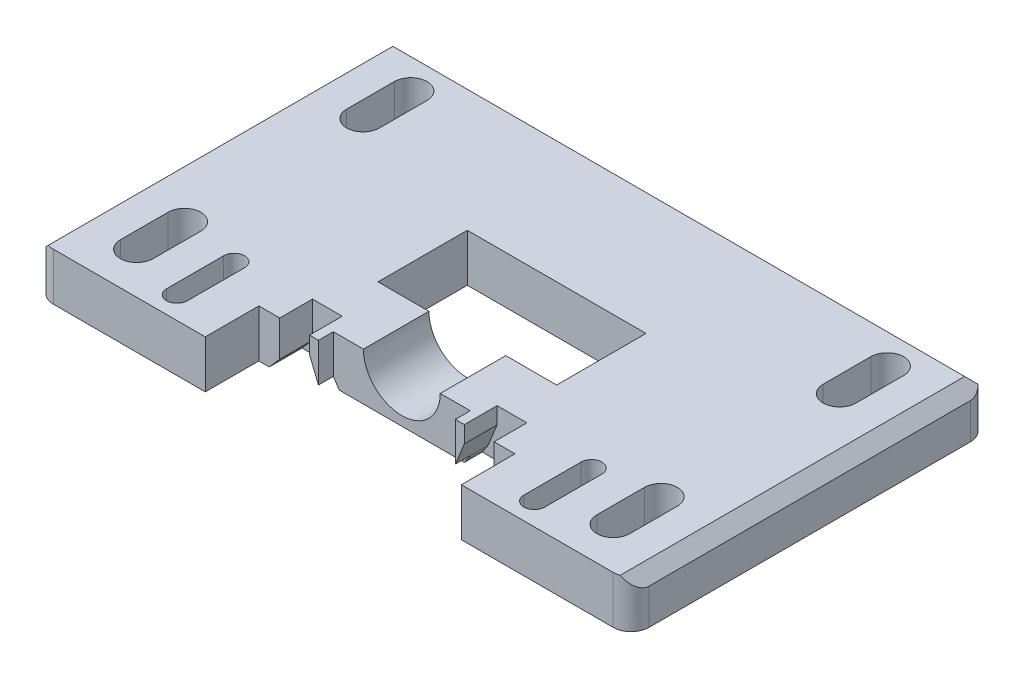
SolidWorks part; units mm, degrees
ref_plane "Front Plane" through (0, 0, 0) normal (0, 0, 1) x (1, 0, 0)
ref_plane "Top Plane" through (0, 0, 0) normal (0, 1, 0) x (1, 0, 0)
ref_plane "Right Plane" through (0, 0, 0) normal (1, 0, 0) x (0, 0, -1)
sketch "Sketch1" plane through (0, 0, 0) normal (0, 1, 0) x (1, 0, 0)
  line L0 (40, 23) -> (40, 15) construction
  line L1 (-50, 30) -> (50, 30)
  line L2 (-50, 30) -> (-50, -30)
  line L3 (-50, -30) -> (50, -30)
  line L4 (50, 30) -> (50, -30)
  line L5 (-15, -7.5) -> (15, -7.5)
  line L6 (-15, -7.5) -> (-15, 7.5)
  line L7 (-15, 7.5) -> (15, 7.5)
  line L8 (15, -7.5) -> (15, 7.5)
  line L9 (-15, -7.5) -> (15, 7.5) construction
  line L10 (-15, 7.5) -> (15, -7.5) construction
  line L11 (42.75, 23) -> (42.75, 15)
  line L12 (37.25, 23) -> (37.25, 15)
  line L13 (40, -23) -> (40, -15) construction
  line L14 (37.25, -23) -> (37.25, -15)
  line L15 (42.75, -23) -> (42.75, -15)
  line L16 (-40, -15) -> (-40, -23) construction
  line L17 (-37.25, -15) -> (-37.25, -23)
  line L18 (-42.75, -15) -> (-42.75, -23)
  line L19 (-40, 23) -> (-40, 15) construction
  line L20 (-37.25, 23) -> (-37.25, 15)
  line L21 (-42.75, 23) -> (-42.75, 15)
  line L22 (-30, -26.25) -> (-30, -16.652) construction
  line L23 (-21.5, -30) -> (21.5, -30)
  line L24 (-21.5, -30) -> (-21.5, -21)
  line L25 (-21.5, -21) -> (21.5, -21)
  line L26 (21.5, -30) -> (21.5, -21)
  line L27 (11.5, -21) -> (-11.5, -21)
  line L28 (11.5, -21) -> (11.5, -18.5)
  line L29 (11.5, -18.5) -> (-11.5, -18.5)
  line L30 (-11.5, -21) -> (-11.5, -18.5)
  line L31 (-31.75, -26.25) -> (-31.75, -16.652)
  line L32 (-28.25, -26.25) -> (-28.25, -16.652)
  line L33 (30, -16.65) -> (30, -26.25) construction
  line L34 (31.75, -16.65) -> (31.75, -26.25)
  line L35 (28.25, -16.65) -> (28.25, -26.25)
  line L37 (13, -21) -> (18, -21)
  line L38 (13, -21) -> (13, -15.5)
  line L39 (13, -15.5) -> (18, -15.5)
  line L40 (18, -21) -> (18, -15.5)
  line L41 (-13, -21) -> (-18, -21)
  line L42 (-13, -21) -> (-13, -15.5)
  line L43 (-13, -15.5) -> (-18, -15.5)
  line L44 (-18, -21) -> (-18, -15.5)
  circle A0 centre (-40, 19) radius 2.75
  circle A1 centre (-40, 19) radius 11.95 construction
  circle A2 centre (40, 19) radius 2.75
  circle A3 centre (-40, -19) radius 2.75
  circle A4 centre (40, -19) radius 2.75
  arc A5 (42.75, 23) -> (37.25, 23) centre (40, 23) ccw
  arc A6 (37.25, 15) -> (42.75, 15) centre (40, 15) ccw
  arc A7 (37.25, -23) -> (42.75, -23) centre (40, -23) ccw
  arc A8 (42.75, -15) -> (37.25, -15) centre (40, -15) ccw
  arc A9 (-37.25, -15) -> (-42.75, -15) centre (-40, -15) ccw
  arc A10 (-42.75, -23) -> (-37.25, -23) centre (-40, -23) ccw
  arc A11 (-37.25, 23) -> (-42.75, 23) centre (-40, 23) ccw
  arc A12 (-42.75, 15) -> (-37.25, 15) centre (-40, 15) ccw
  arc A13 (-31.75, -26.25) -> (-28.25, -26.25) centre (-30, -26.25) ccw
  arc A14 (-28.25, -16.652) -> (-31.75, -16.652) centre (-30, -16.652) ccw
  arc A15 (31.75, -16.65) -> (28.25, -16.65) centre (30, -16.65) ccw
  arc A16 (28.25, -26.25) -> (31.75, -26.25) centre (30, -26.25) ccw
  point P14 (0, 0)
  point P21 (40, 19)
  point P28 (40, -19)
  point P35 (-40, -19)
  point P42 (-40, 19)
  point P51 (0, -21)
  point P56 (0, -18.5)
  point P59 (-30, -21.451)
  point P66 (30, -21.45)
  dimension "D5" = 5.5
  dimension "D8" = 23.9
  dimension "D9" = 5.5
  dimension "D10" = 10
  dimension "D12" = 5.5
  dimension "D13" = 11
  dimension "D14" = 10
  dimension "D15" = 11
  dimension "D16" = 5.5
  dimension "D33" = 10
  dimension "D1" = 60
  dimension "D2" = 100
  dimension "D3" = 50
  dimension "D4" = 30
  dimension "D6" = 10
  dimension "D7" = 11
  dimension "D11" = 11
  dimension "10" = 10
  dimension "D17" = 15
  dimension "D18" = 30
  dimension "D19" = 5.5
  dimension "D20" = 8
  dimension "D21" = 5.5
  dimension "D22" = 8
  dimension "D23" = 5.5
  dimension "D24" = 8
  dimension "D25" = 5.5
  dimension "D26" = 8
  dimension "D27" = 43
  dimension "D28" = 9
  dimension "D29" = 2.5
  dimension "D30" = 23
  dimension "D31" = 3.5
  dimension "D32" = 9.598
  dimension "D34" = 3.75
  dimension "D35" = 3.5
  dimension "D36" = 9.6
  dimension "D37" = 10
  dimension "D38" = 3.75
  dimension "D39" = 13
  dimension "D40" = 5
  dimension "D41" = 5.5
  dimension "D42" = 5
  dimension "D43" = 13
  dimension "D44" = 5.5
sketch "Sketch2" plane through (0, 0, 0) normal (0, 1, 0) x (1, 0, 0)
  line L0 (-100, -10) -> (100, 10) construction
  line L1 (-100, 10) -> (100, 10) construction
  line L2 (-100, 10) -> (-100, -10) construction
  line L3 (-100, -10) -> (100, -10) construction
  line L4 (100, 10) -> (100, -10) construction
  dimension "D1" = 200
  dimension "D2" = 20
extrude "Boss-Extrude1" add sketch "Sketch1" along normal blind 8 contours L4 L1 L2 L3 A12 L21 A11 L20 A10 L18 A9 L17 A8 L15 A7 L14 A6 L12 A5 L11 L8 L5 L6 L7 region at (0, 0, -28.8338)
sketch "Sketch4" plane through (0, 0, 18.5) normal (0, 0, 1) x (1, 0, 0)
  line L0 (11.5, 8) -> (-11.5, 8) construction
  circle A0 centre (0, 8) radius 6.45
  dimension "D1" = 12.9
extrude "Cut-Extrude1" cut sketch "Sketch4" against normal up to surface (11 mm away) up to face at (0, 4, 7.5)
sketch "Sketch5" plane through (0, 0, 21) normal (0, 0, 1) x (1, 0, 0)
  line L0 (13, 5.2) -> (11.5, 1.5)
  line L2 (11.5, 8) -> (11.5, 0) construction
  line L3 (18, 2) -> (19.75, 0)
  line L4 (18, 8) -> (18, 0) construction
  line L5 (18, 0) -> (21.5, 0) construction
  line L6 (21.5, 0) -> (21.5, 8) construction
  line L7 (21.5, 8) -> (18, 8) construction
  line L8 (11.5, 0) -> (13, 0) construction
  line L9 (13, 0) -> (13, 8) construction
  line L10 (13, 8) -> (11.5, 8) construction
  line L11 (18, 0) -> (21.5, 0)
  line L12 (21.5, 0) -> (21.5, 8)
  line L13 (21.5, 8) -> (18, 8)
  line L14 (18, 8) -> (18, 0)
  line L15 (11.5, 0) -> (13, 0)
  line L16 (13, 0) -> (13, 8)
  line L17 (13, 8) -> (11.5, 8)
  line L18 (11.5, 8) -> (11.5, 0)
  line L19 (13, 8) -> (13, 0) construction
  line L21 (-21.5, 0) -> (-18, 0) construction
  line L22 (-18, 0) -> (-18, 8) construction
  line L23 (-18, 8) -> (-21.5, 8) construction
  line L24 (-21.5, 8) -> (-21.5, 0) construction
  line L25 (-13, 0) -> (-11.5, 0) construction
  line L26 (-11.5, 0) -> (-11.5, 8) construction
  line L27 (-11.5, 8) -> (-13, 8) construction
  line L28 (-13, 8) -> (-13, 0) construction
  line L29 (-21.5, 0) -> (-18, 0)
  line L30 (-18, 0) -> (-18, 8)
  line L31 (-18, 8) -> (-21.5, 8)
  line L32 (-21.5, 8) -> (-21.5, 0)
  line L33 (-13, 0) -> (-11.5, 0)
  line L34 (-11.5, 0) -> (-11.5, 8)
  line L35 (-11.5, 8) -> (-13, 8)
  line L36 (-13, 8) -> (-13, 0)
  line L37 (-13, 5.2) -> (-11.5, 1.5)
  line L38 (-18, 2) -> (-19.75, 0)
  line L39 (11.5, 1.5) -> (10.5, 0)
  line L40 (-11.5, 1.5) -> (-10.5, 0)
  line L44 (-6.45, 8) -> (-11.5, 8)
  line L45 (-11.5, 8) -> (-11.5, 0)
  line L46 (-11.5, 0) -> (11.5, 0)
  line L47 (11.5, 0) -> (11.5, 8)
  line L48 (11.5, 8) -> (6.45, 8)
  line L49 (-6.45, 8) -> (-11.5, 8)
  line L50 (-11.5, 8) -> (-11.5, 0)
  line L51 (-11.5, 0) -> (11.5, 0)
  line L52 (11.5, 0) -> (11.5, 8)
  line L53 (11.5, 8) -> (6.45, 8)
  arc A1 (-6.45, 8) -> (6.45, 8) centre (0, 8) ccw
  arc A2 (-6.45, 8) -> (6.45, 8) centre (0, 8) ccw
  point P4 (0, 0)
  line M1 (18, 0) -> (21.5, 0)
  line M4 (18, 8) -> (18, 0)
  dimension "D1" = 1.5
  dimension "D2" = 2
  dimension "D3" = 5.2
  dimension "D4" = 5.2
  dimension "D5" = 1.5
  dimension "D6" = 2
  dimension "D8" = 1
  dimension "D9" = 1
  dimension "D7" = 0
extrude "Cut-Extrude2" cut sketch "Sketch5" against normal up to surface (5.5 mm away) contours L0 L18 L15 L16 | L3 M4 M1 | L37 L36 L33 L34 | L30 L38 L29 | L39 L51 L18 | L34 L51 L40 region at (12.3881, 1.8453, 21) region at (11.1667, 0.5, 21) region at (-11.1667, 0.5, 21) region at (-12.3881, 1.8453, 21) region at (18.5833, 0.6667, 21) region at (-18.5833, 0.6667, 21) up to face at (15.5, 4, 15.5)
chamfer "Chamfer1" distance 2 angle 45 3 edges at (50, 8, 0) (0, 8, -30) (-50, 8, 0)
fillet "Fillet1" radius 3 4 edges at (-50, 3, 30) (50, 3, 30) (50, 3, -30) (-50, 3, -30)
